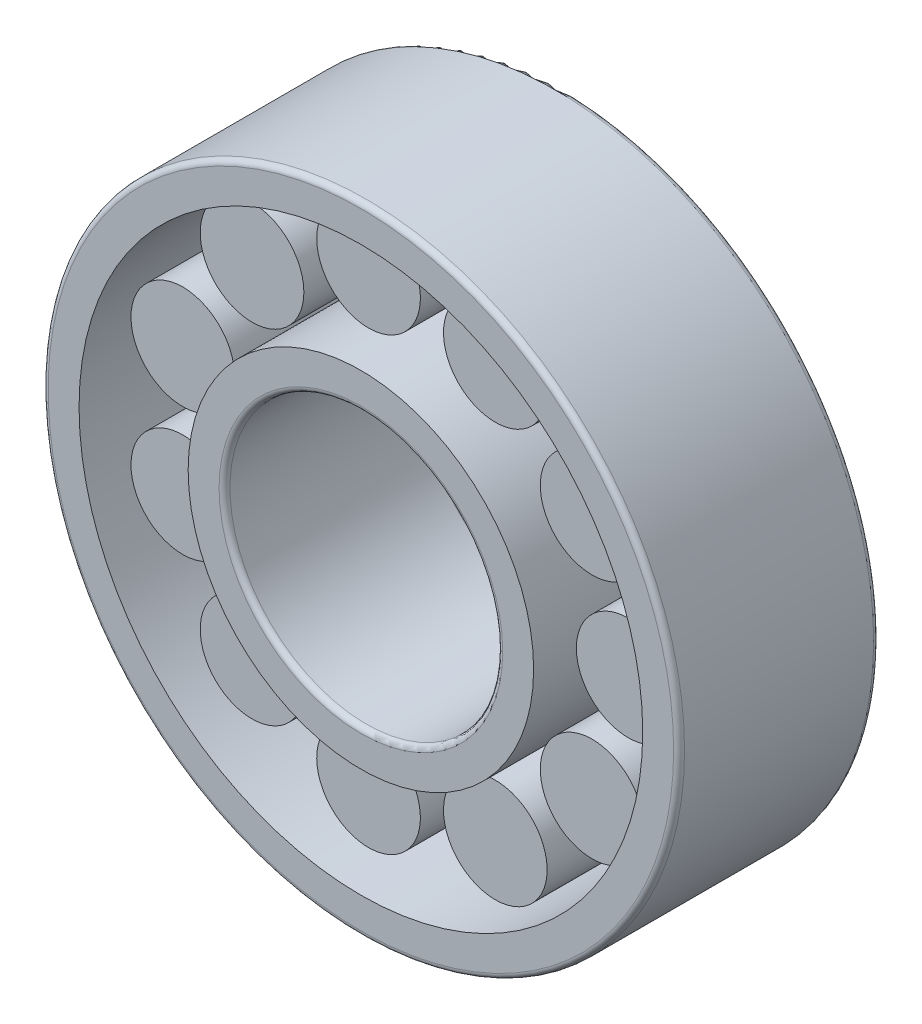
SolidWorks part; units mm, degrees
ref_plane "Front Plane" through (0, 0, 0) normal (0, 0, 1) x (1, 0, 0)
ref_plane "Top Plane" through (0, 0, 0) normal (0, 1, 0) x (1, 0, 0)
ref_plane "Right Plane" through (0, 0, 0) normal (1, 0, 0) x (0, 0, -1)
sketch "S" plane through (0, 0, 0) normal (0, 0, 1) x (1, 0, 0)
  line L0 (-5.5, 0) -> (5.5, 0) construction
  circle A0 centre (0, 0) radius 7.5 construction
  circle A1 centre (0, 0) radius 17.5 construction
  circle A2 centre (0, 0) radius 9.5 construction
  circle A3 centre (0, 0) radius 15.5 construction
  dimension "ID" = 15
  dimension "OD" = 35
  dimension "IDa" = 19
  dimension "ODa" = 31
  dimension "B" = 11
ref_axis "Z" through (0, 0, -6.05) along (0, 0, 1)
sketch "InnerS" plane through (0, 0, 0) normal (0, 1, 0) x (1, 0, 0)
  line L0 (7.5, -5.5) -> (9.5, -5.5)
  line L1 (9.5, -5.5) -> (9.5, 5.5)
  line L2 (9.5, 5.5) -> (7.5, 5.5)
  line L3 (7.5, 5.5) -> (7.5, -5.5)
  line L4 (0, -9.25) -> (0, 9.25) construction
  dimension "r1" = 7.5
  dimension "r2" = 9.5
  dimension "z1" = 5.5
  dimension "z2" = 5.5
revolve "InnerRing" add sketch "InnerS" angle 360 about L4
sketch "OuterS" plane through (0, 0, 0) normal (0, 1, 0) x (1, 0, 0)
  line L0 (15.5, -5.5) -> (17.5, -5.5)
  line L1 (17.5, -5.5) -> (17.5, 5.5)
  line L2 (17.5, 5.5) -> (15.5, 5.5)
  line L3 (15.5, 5.5) -> (15.5, -5.5)
  line L4 (0, -9.25) -> (0, 9.25) construction
  dimension "z1" = 5.5
  dimension "z2" = 5.5
  dimension "r1" = 15.5
  dimension "r2" = 17.5
revolve "OuterRing" add sketch "OuterS" angle 360 about L4
sketch "RollerS" plane through (0, 0, 0) normal (0, 1, 0) x (1, 0, 0)
  line L0 (12.5, -3.3) -> (15.35, -3.3)
  line L1 (15.35, -3.3) -> (15.35, 3.3)
  line L2 (15.35, 3.3) -> (12.5, 3.3)
  line L3 (12.5, 3.3) -> (12.5, -3.3)
  dimension "r1" = 12.5
  dimension "r2" = 15.35
  dimension "z1" = 3.3
  dimension "z2" = 3.3
revolve "Roller" add sketch "RollerS" angle 360 about L3
pattern_circular "RollersPattern" count 11 over 360 about axis through (0, 0, -6.05) along (0, 0, 1) of bodies 103
fillet "F1" radius 0.3 2 edges at (17.5, 0, -5.5) (17.5, 0, 5.5)
fillet "F2" radius 0.3 2 edges at (7.5, 0, -5.5) (7.5, 0, 5.5)
equation "\"r1@InnerS\" = abs(0.5*\"ID@S\")"
equation "\"r2@InnerS\" = abs(0.5*\"IDa@S\")"
equation "\"z1@InnerS\" = abs(-0.5*\"B@S\")"
equation "\"z2@InnerS\" = abs(0.5*\"B@S\")"
equation "\"r1@OuterS\" = abs(0.5*\"ODa@S\")"
equation "\"r2@OuterS\" = abs(0.5*\"OD@S\")"
equation "\"z1@OuterS\" = abs(-0.5*\"B@S\")"
equation "\"z2@OuterS\" = abs(0.5*\"B@S\")"
equation "\"r1@RollerS\" = abs(0.25*\"IDa@S\"+0.25*\"ODa@S\")"
equation "\"r2@RollerS\" = abs(0.0125*\"IDa@S\"+0.4875*\"ODa@S\")"
equation "\"z1@RollerS\" = abs(-0.3*\"B@S\")"
equation "\"z2@RollerS\" = abs(0.3*\"B@S\")"
equation "\"N@RollersPattern\" = int(5.027*(0.25*\"IDa@S\"+0.25*\"ODa@S\")/(0.475*\"ODa@S\"-0.475*\"IDa@S\"))"
equation "\"r_min@F2\" = \"r_min@F1\""
